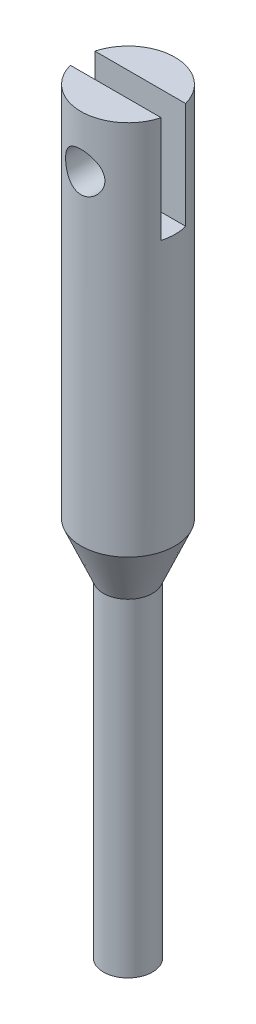
SolidWorks part; units mm, degrees
ref_plane "Front Plane" through (0, 0, 0) normal (0, 0, 1) x (1, 0, 0)
ref_plane "Top Plane" through (0, 0, 0) normal (0, 1, 0) x (1, 0, 0)
ref_plane "Right Plane" through (0, 0, 0) normal (1, 0, 0) x (0, 0, -1)
sketch "Sketch1" plane through (0, 0, 0) normal (0, 0, 1) x (1, 0, 0)
  line L0 (0, 0) -> (1.5, 0)
  line L1 (1.5, 0) -> (1.5, 20.05)
  line L2 (1.5, 20.05) -> (2.875, 23.25)
  line L3 (2.875, 23.25) -> (2.875, 46.25)
  line L4 (2.875, 46.25) -> (0, 46.25)
  line L5 (0, 46.25) -> (0, 0)
  dimension "D1" = 23
  dimension "D2" = 2.875
  dimension "D3" = 1.5
  dimension "D4" = 46.25
  dimension "D5" = 26.2
revolve "Revolve1" add sketch "Sketch1" angle 360 about L5
sketch "Sketch2" plane through (0, 0, 0) normal (0, 0, 1) x (1, 0, 0)
  line L0 (2.875, 46.25) -> (-2.875, 46.25) construction
  line L1 (0, 46.25) -> (0, 44.25) construction
  circle A0 centre (0, 43.05) radius 1.2
  point P2 (0, 44.25)
  dimension "D1" = 2.4
  dimension "D2" = 2
extrude "Cut-Extrude1" cut sketch "Sketch2" against normal through all both and the other way through all
sketch "Sketch3" plane through (0, 46.25, 0) normal (0, 1, 0) x (1, 0, 0)
  line L0 (0, 0) -> (-2.875, 0) construction
  line L5 (-2.875, 0.75) -> (2.875, 0.75)
  line L6 (-2.875, 0.75) -> (-2.875, -0.75)
  line L7 (-2.875, -0.75) -> (2.875, -0.75)
  line L8 (2.875, 0.75) -> (2.875, -0.75)
  circle A1 centre (0, 0) radius 2.875 construction
  dimension "D1" = 1.5
extrude "Cut-Extrude2" cut sketch "Sketch3" against normal blind 6.5
